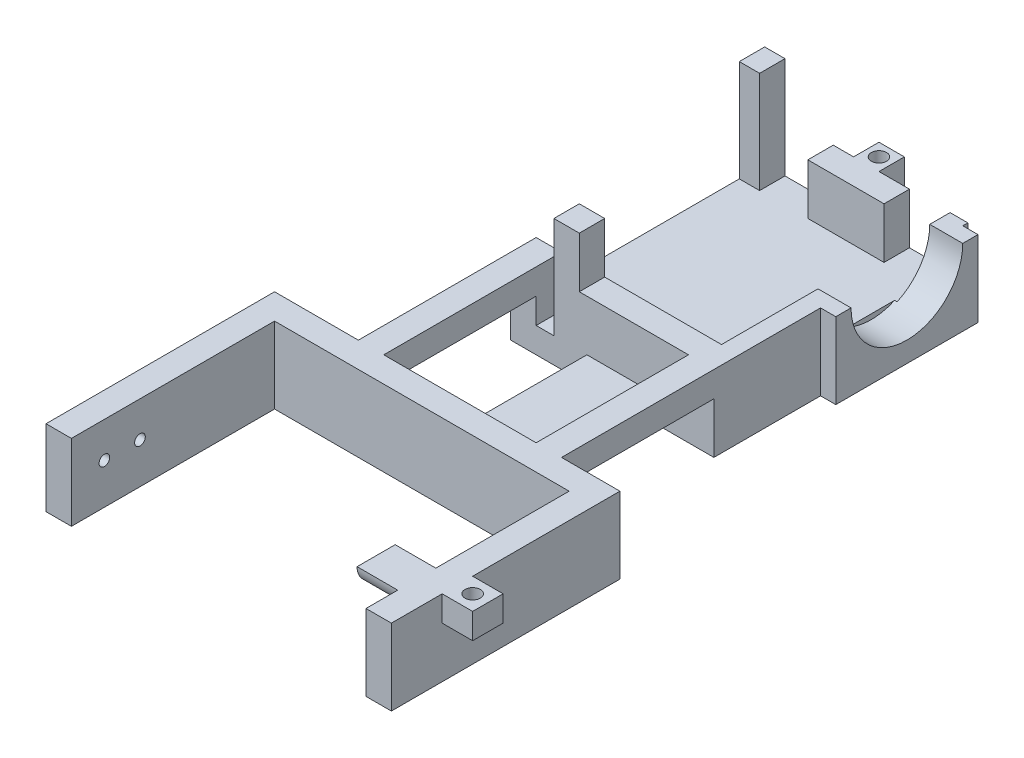
SolidWorks part; units mm, degrees
ref_plane "Front Plane" through (0, 0, 0) normal (0, 0, 1) x (1, 0, 0)
ref_plane "Top Plane" through (0, 0, 0) normal (0, 1, 0) x (1, 0, 0)
ref_plane "Right Plane" through (0, 0, 0) normal (1, 0, 0) x (0, 0, -1)
sketch "Sketch1" plane through (0, 0, 0) normal (0, 1, 0) x (1, 0, 0)
  line L1 (-20, 25) -> (20, 25)
  line L2 (-20, 25) -> (-20, -25)
  line L3 (-20, -25) -> (20, -25)
  line L4 (20, 25) -> (20, -25)
  point P5 (-20, 0)
  point P6 (0, 25)
  dimension "D1" = 40
  dimension "D2" = 50
extrude "Boss-Extrude1" add sketch "Sketch1" along normal blind 5
sketch "Sketch4" plane through (0, 5, 0) normal (0, 1, 0) x (1, 0, 0)
  line L0 (-20, -25) -> (20, -25) construction
  line L1 (20, 25) -> (16.5, 25)
  line L2 (20, 25) -> (20, -25)
  line L4 (16.5, 25) -> (16.5, -20)
  line L5 (20, 25) -> (-20, 25) construction
  line L8 (16.5, -20) -> (-6.5, -20)
  line L9 (-6.5, -25) -> (-6.5, -20)
  line L10 (-20, 25) -> (-16, 25)
  line L11 (-20, 25) -> (-20, 20)
  line L12 (-20, 20) -> (-16, 20)
  line L13 (-16, 25) -> (-16, 20)
  line L14 (-6.5, 25) -> (8.5, 25)
  line L15 (-6.5, 25) -> (-6.5, 20)
  line L16 (-6.5, 20) -> (8.5, 20)
  line L17 (8.5, 25) -> (8.5, 20)
  line L18 (-6.5, -25) -> (20, -25)
  line L19 (-11.5, 25) -> (-11.5, 20) construction
  line L20 (-11.5, 20) -> (-6.5, 20) construction
  line L21 (-15, -20) -> (-15, -25)
  line L22 (-15, -20) -> (-20, -20)
  line L24 (-15, -25) -> (-15, -20) construction
  line L25 (-6.5, -20) -> (-11.5, -20)
  line L26 (-6.5, -20) -> (-6.5, -25)
  line L27 (-6.5, -25) -> (-11.5, -25)
  line L28 (-11.5, -20) -> (-11.5, -25)
  line L29 (-20, 25) -> (-20, -25) construction
  line L30 (-20, -20) -> (-15, -20) construction
  line L31 (-20, -20) -> (-20, -25)
  line L32 (-20, -25) -> (-15, -25)
  line M19 (-20, 25) -> (-20, -25)
  line M20 (-20, -25) -> (20, -25)
  line M21 (20, -25) -> (20, 25)
  line M22 (20, 25) -> (-20, 25)
  dimension "D1" = 3.5
  dimension "D2" = 5
  dimension "D3" = 4
  dimension "D4" = 15
  dimension "D5" = 5
  dimension "D6" = 8
extrude "Boss-Extrude4" add sketch "Sketch4" along normal blind 20 contours L25 L28 L9 M20 | L13 L12 M22 M19 region at (-9, 5, 22.5) region at (-18, 5, -22.5)
extrude "Boss-Extrude5" add sketch "Sketch4<4>" along normal blind 10 contours L9 L4 L8 M20 M21 M22 | L17 L15 L16 M22 | L32 L21 L22 L31 region at (19.4341, 5, 0) region at (1, 5, -22.5)
sketch "Sketch4<4>" plane through (0, 5, 0) normal (0, 1, 0) x (1, 0, 0) same geometry as "Sketch4"
sketch "Sketch7" plane through (20, 0, 0) normal (1, 0, 0) x (0, 0, -1)
  line L0 (-25, 15) -> (25, 15) construction
  line L1 (-1, 15) -> (21, 15)
  line L2 (25, 25) -> (25, 5) construction
  arc A0 (-1, 15) -> (21, 15) centre (10, 15) ccw
  dimension "D1" = 22
extrude "Cut-Extrude2" cut sketch "Sketch7" against normal blind 4
sketch "Sketch8" plane through (20, 0, 0) normal (1, 0, 0) x (0, 0, -1)
  line L0 (-1, 15) -> (-4, 15)
  line L1 (-25, 15) -> (-1, 15) construction
  line L2 (-4, 15) -> (-4, 0)
  line L3 (-25, 0) -> (25, 0) construction
  line L4 (-4, 0) -> (24, 0)
  line L5 (24, 0) -> (24, 15)
  line L6 (21, 15) -> (25, 15) construction
  line L7 (24, 15) -> (21, 15)
  arc A0 (-1, 15) -> (21, 15) centre (10, 15) ccw
  dimension "D2" = 22
  dimension "D1" = 3
extrude "Boss-Extrude7" add sketch "Sketch8" along normal blind 3
sketch "Sketch10" plane through (0, 0, -25) normal (0, 0, -1) x (-1, 0, 0)
  line L0 (-8.5, 15) -> (6.5, 15) construction
  line L1 (-2.5, 15) -> (2.5, 15)
  line L2 (-2.5, 15) -> (-2.5, 10)
  line L3 (-2.5, 10) -> (2.5, 10)
  line L4 (2.5, 15) -> (2.5, 10)
  line L5 (-20, 0) -> (20, 0) construction
  point P8 (0, 0)
  point P9 (0, 10)
  dimension "D1" = 5
  dimension "D2" = 5
extrude "Boss-Extrude9" add sketch "Sketch10" along normal blind 5
sketch "Sketch11" plane through (0, 10, 0) normal (0, -1, 0) x (1, 0, 0)
  line L0 (2.5, -30) -> (-2.5, -30) construction
  line L1 (2.5, -30) -> (2.5, -25) construction
  circle A0 centre (0, -27.5) radius 1.5
  point P4 (0, -30)
  point P7 (2.5, -27.5)
  dimension "D1" = 3
extrude "Cut-Extrude3" cut sketch "Sketch11" against normal blind 5
sketch "Sketch12" plane through (0, 0, 25) normal (0, 0, 1) x (1, 0, 0)
  line L0 (-20, 15) -> (-20, 0) construction
  line L1 (-15, 15) -> (-20, 15)
  line L2 (-15, 15) -> (-15, 10)
  line L3 (-15, 10) -> (-20, 10)
  line L4 (-20, 15) -> (-20, 10)
  line L5 (-20, 0) -> (20, 0) construction
  line L6 (20, 15) -> (15, 15)
  line L7 (20, 15) -> (20, 10)
  line L8 (20, 10) -> (15, 10)
  line L9 (15, 15) -> (15, 10)
  line L10 (-5, 0) -> (5, 0)
  line L11 (-5, 0) -> (-5, 5)
  line L12 (-5, 5) -> (5, 5)
  line L13 (5, 0) -> (5, 5)
  point P18 (0, 5)
  dimension "D1" = 5
  dimension "D2" = 5
  dimension "D3" = 10
extrude "Boss-Extrude10" add sketch "Sketch12" along normal blind 30
sketch "Sketch13" plane through (0, 0, 55) normal (0, 0, 1) x (1, 0, 0)
  line L0 (-20, 15) -> (-20, 10) construction
  line L1 (20, 0) -> (-20, 0)
  line L2 (20, 0) -> (20, 15)
  line L3 (20, 15) -> (-20, 15)
  line L4 (-20, 0) -> (-20, 15)
  line L5 (-5, 0) -> (5, 0) construction
extrude "Boss-Extrude11" add sketch "Sketch13" along normal blind 5
sketch "Sketch14" plane through (20, 0, 0) normal (1, 0, 0) x (0, 0, -1)
  line L1 (-55, 0) -> (-60, 0)
  line L2 (-55, 0) -> (-55, 15)
  line L3 (-55, 15) -> (-60, 15)
  line L4 (-60, 0) -> (-60, 15)
extrude "Boss-Extrude12" add sketch "Sketch14" along normal blind 11.5
sketch "Sketch15" plane through (-20, 0, 0) normal (-1, 0, 0) x (0, 0, 1)
  line L1 (55, 0) -> (60, 0)
  line L2 (55, 0) -> (55, 15)
  line L3 (55, 15) -> (60, 15)
  line L4 (60, 0) -> (60, 15)
extrude "Boss-Extrude13" add sketch "Sketch15" along normal blind 16.5
sketch "Sketch16" plane through (0, 0, 60) normal (0, 0, 1) x (1, 0, 0)
  line L0 (-36.5, 0) -> (31.5, 0) construction
  line L1 (-36.5, 15) -> (-31.5, 15)
  line L2 (-36.5, 15) -> (-36.5, 0)
  line L3 (-36.5, 0) -> (-31.5, 0)
  line L4 (-31.5, 15) -> (-31.5, 0)
  line L6 (31.5, 15) -> (26.5, 15)
  line L7 (31.5, 15) -> (31.5, 0)
  line L8 (31.5, 0) -> (26.5, 0)
  line L9 (26.5, 15) -> (26.5, 0)
  dimension "D1" = 5
extrude "Boss-Extrude14" add sketch "Sketch16" along normal blind 40
sketch "Sketch17" plane through (26.5, 0, 0) normal (-1, 0, 0) x (0, 0, 1)
  line L0 (100, 15) -> (100, 0) construction
  line L1 (100, 15) -> (55, 15) construction
  line L2 (86.25, 15) -> (93.75, 15)
  arc A0 (86.25, 15) -> (93.75, 15) centre (90, 15) ccw
  dimension "D1" = 7.5
  dimension "D2" = 10
extrude "Boss-Extrude15" add sketch "Sketch17" along normal blind 8
sketch "Sketch20" plane through (31.5, 0, 0) normal (1, 0, 0) x (0, 0, -1)
  line L0 (-55, 15) -> (-100, 15) construction
  line L1 (-84, 10) -> (-90, 10)
  line L2 (-84, 10) -> (-84, 15)
  line L3 (-84, 15) -> (-90, 15)
  line L4 (-90, 10) -> (-90, 15)
  line L5 (-100, 0) -> (-100, 15) construction
  dimension "D1" = 6
  dimension "D2" = 5
  dimension "D3" = 10
extrude "Boss-Extrude17" add sketch "Sketch20" along normal blind 6
sketch "Sketch21" plane through (0, 10, 0) normal (0, -1, 0) x (1, 0, 0)
  line L0 (37.5, 90) -> (37.5, 84) construction
  line L1 (37.5, 90) -> (31.5, 90) construction
  circle A0 centre (34.5, 87) radius 1.5
  point P4 (37.5, 87)
  point P7 (34.5, 90)
  dimension "D1" = 3
extrude "Cut-Extrude5" cut sketch "Sketch21" against normal blind 5
sketch "Sketch24" plane through (-31.5, 0, 0) normal (1, 0, 0) x (0, 0, -1)
  line L0 (-93.5, 8) -> (-86.5, 8) construction
  line L1 (-100, 15) -> (-60, 15) construction
  line L2 (-90, 15) -> (-83, 15) construction
  line L5 (-90, 15) -> (-97, 15) construction
  circle A0 centre (-93.5, 8) radius 1.05
  circle A1 centre (-86.5, 8) radius 1.05
  dimension "D6" = 2.1
  dimension "D1" = 7
  dimension "D2" = 7
  dimension "D3" = 7
  dimension "D4" = 3
  dimension "D5" = 7
extrude "Cut-Extrude6" cut sketch "Sketch24" against normal blind 5
